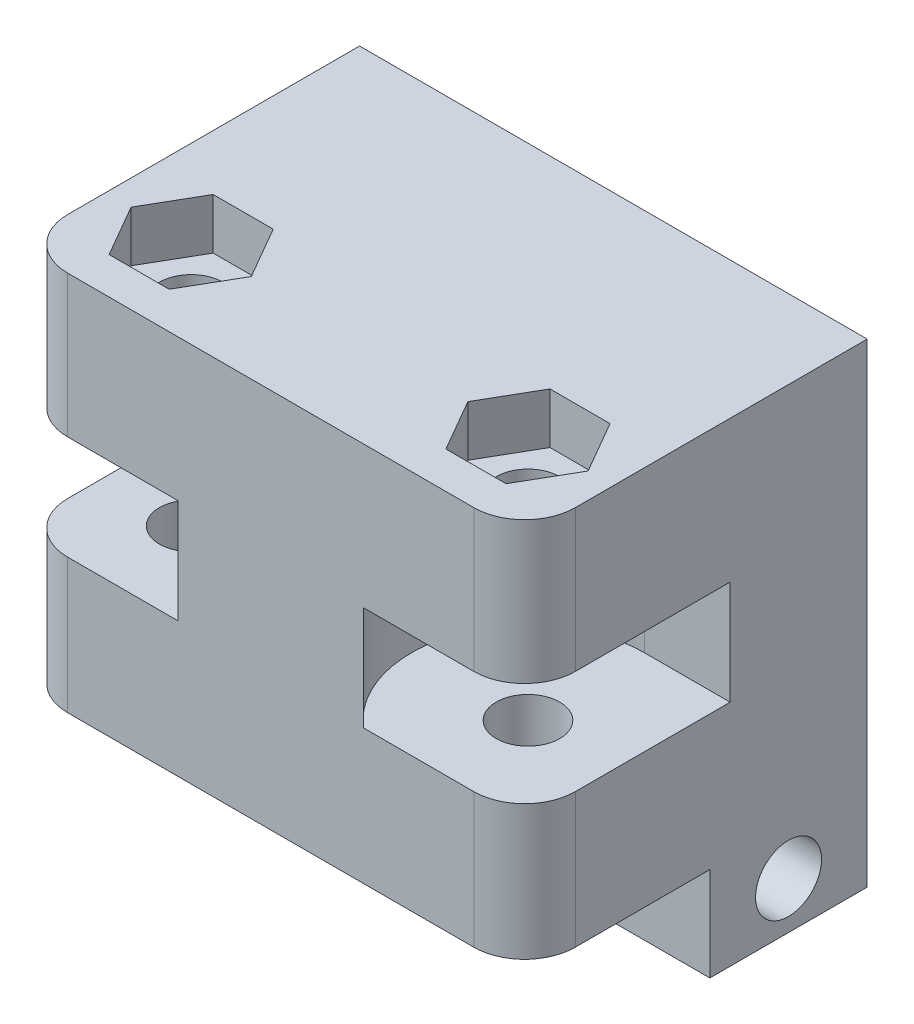
SolidWorks part; units mm, degrees
ref_plane "Front Plane" through (0, 0, 0) normal (0, 0, 1) x (1, 0, 0)
ref_plane "Top Plane" through (0, 0, 0) normal (0, 1, 0) x (1, 0, 0)
ref_plane "Right Plane" through (0, 0, 0) normal (1, 0, 0) x (0, 0, -1)
sketch "Sketch1" plane through (0, 0, 0) normal (0, 1, 0) x (1, 0, 0)
  line L1 (-22.8462, -9.1868) -> (17.1538, -9.1868)
  line L2 (-22.8462, -9.1868) -> (-22.8462, 17.8132)
  line L3 (-22.8462, 17.8132) -> (17.1538, 17.8132)
  line L4 (17.1538, -9.1868) -> (17.1538, 17.8132)
  dimension "D1" = 27
  dimension "D2" = 40
extrude "Boss-Extrude1" add sketch "Sketch1" along normal blind 30
sketch "Sketch2" plane through (0, 0, -17.8132) normal (0, 0, -1) x (-1, 0, 0)
  line L0 (2.8462, 30) -> (2.8462, 0) construction
  line L1 (-8.0864, 4) -> (-0.2064, 4)
  line L2 (-0.2064, 4) -> (-0.2064, 7)
  line L3 (-0.2064, 7) -> (-2.8664, 7)
  line L4 (-2.8664, 7) -> (-2.8664, 8.0087)
  line L5 (-2.8664, 8.0087) -> (-0.2538, 10.6287)
  line L6 (-0.2538, 10.6287) -> (5.9462, 10.6287)
  line L7 (-17.1538, 30) -> (22.8462, 30) construction
  line L8 (-17.1538, 0) -> (22.8462, 0) construction
  line L9 (-8.0864, 4) -> (-8.0864, 26)
  line L10 (-8.0864, 26) -> (-0.2064, 26)
  line L11 (-0.2064, 26) -> (-0.2064, 23)
  line L12 (-0.2064, 23) -> (-2.8664, 23)
  line L13 (-2.8664, 23) -> (-2.8664, 21.9913)
  line L14 (-2.8664, 21.9913) -> (-0.2464, 19.3787)
  line L15 (-0.2464, 19.3787) -> (5.9536, 19.3787)
  line L16 (-17.1538, 15) -> (22.8462, 15) construction
  line L17 (-17.1538, 30) -> (-17.1538, 0) construction
  line L18 (22.8462, 30) -> (22.8462, 0) construction
  line L19 (5.9387, 19.3787) -> (-0.2613, 19.3787)
  line L20 (8.5587, 21.9913) -> (5.9387, 19.3787)
  line L21 (8.5587, 23) -> (8.5587, 21.9913)
  line L22 (5.8987, 23) -> (8.5587, 23)
  line L23 (5.8987, 26) -> (5.8987, 23)
  line L24 (13.7787, 26) -> (5.8987, 26)
  line L25 (13.7787, 4) -> (13.7787, 26)
  line L26 (8.5587, 8.0087) -> (5.9462, 10.6287)
  line L27 (8.5587, 7) -> (8.5587, 8.0087)
  line L28 (5.8987, 7) -> (8.5587, 7)
  line L29 (5.8987, 4) -> (5.8987, 7)
  line L30 (13.7787, 4) -> (5.8987, 4)
  point P26 (-8.0864, 15)
  point P27 (2.8462, 15)
  point P37 (2.8462, 10.6287)
  dimension "D1" = 6.2
  dimension "D2" = 2.62
  dimension "D3" = 3.7
  dimension "D4" = 8.75
  dimension "D5" = 7.88
  dimension "D6" = 22
  dimension "D7" = 5.22
  dimension "D8" = 3
  dimension "D9" = 90
extrude "Cut-Extrude1" cut sketch "Sketch2" against normal blind 10 contours L30 L25 L24 L23 L22 L21 L20 L15 L14 L13 L12 L11 L10 L9 L1 L2 L3 L4 L5 L6 L26 L27 L28 L29 region at (-2.8462, 15.0011, -17.8132)
sketch "Sketch3" plane through (0, 0, 0) normal (0, -1, 0) x (1, 0, 0)
  line L0 (-22.8462, 9.1868) -> (17.1538, 9.1868) construction
  line L1 (17.1538, 9.1868) -> (17.1538, -17.8132) construction
  line L2 (-2.8462, 9.1868) -> (-2.8462, -17.8132) construction
  line L3 (17.1538, -17.8132) -> (-22.8462, -17.8132) construction
  circle A0 centre (10.4238, 2.1868) radius 2.5
  circle A2 centre (-16.1162, 2.1868) radius 2.5
  dimension "D1" = 5
  dimension "D3" = 7
  dimension "D4" = 6.73
extrude "Cut-Extrude2" cut sketch "Sketch3" against normal blind 30
sketch "Sketch8" plane through (0, 0, 0) normal (0, -1, 0) x (1, 0, 0)
  line L0 (4.4539, 9.1868) -> (17.1538, 9.1868)
  line L1 (-22.8462, 9.1868) -> (17.1538, 9.1868) construction
  line L2 (17.1538, 9.1868) -> (17.1538, -7.0132)
  line L3 (17.1538, 9.1868) -> (17.1538, -17.8132) construction
  line L4 (17.1538, -7.0132) -> (10.4238, -7.0132)
  line L6 (-2.8462, -17.8132) -> (-2.8462, 9.1868) construction
  line L7 (17.1538, -17.8132) -> (-22.8462, -17.8132) construction
  line L8 (-22.8462, -7.0132) -> (-16.1162, -7.0132)
  line L9 (-22.8462, 9.1868) -> (-22.8462, -7.0132)
  line L10 (-10.1462, 9.1868) -> (-22.8462, 9.1868)
  arc A0 (10.4238, -7.0132) -> (4.4539, 9.1868) centre (10.4238, 2.1868) cw
  arc A1 (-16.1162, -7.0132) -> (-10.1462, 9.1868) centre (-16.1162, 2.1868) ccw
  circle M6 centre (10.4238, 2.1868) radius 2.5
  circle M7 centre (-16.1162, 2.1868) radius 2.5
  line M8 (-22.8462, 9.1868) -> (-22.8462, -17.8132)
  line M10 (17.1538, -17.8132) -> (17.1538, 9.1868)
  line M11 (17.1538, 9.1868) -> (-22.8462, 9.1868)
  dimension "D1" = 9.2
  dimension "D2" = 6.73
extrude "Cut-Extrude5" cut sketch "Sketch8" against normal blind 8.2 from offset 10.62 contours A0 L4 M10 M11 M6 | M6 | L8 A1 M11 M8 M7 | M7 region at (10.8039, 0, 8.9596) region at (-7.6968, 0, -0.9158) region at (10.4238, 0, 2.1868) region at (-16.1162, 0, 2.1868) offset against normal yes
sketch "Sketch10" plane through (8.0864, 0, 0) normal (-1, 0, 0) x (0, 0, 1)
  line L0 (-17.8132, 30) -> (-17.8132, 0) construction
  line L1 (-17.8132, 18.82) -> (2.1868, 18.82)
  line L2 (-17.8132, 18.82) -> (-17.8132, 10.62)
  line L3 (-17.8132, 10.62) -> (2.1868, 10.62)
  line L4 (2.1868, 18.82) -> (2.1868, 10.62)
  line L5 (-17.8132, 30) -> (9.1868, 30) construction
  dimension "D1" = 20
  dimension "D2" = 11.18
  dimension "D3" = 8.2
extrude "Cut-Extrude7" cut sketch "Sketch10" along normal blind 6.8
sketch "Sketch12" plane through (-13.7787, 0, 0) normal (1, 0, 0) x (0, 0, -1)
  line L1 (17.8132, 18.82) -> (-2.1868, 18.82)
  line L2 (17.8132, 18.82) -> (17.8132, 10.62)
  line L3 (17.8132, 10.62) -> (-2.1868, 10.62)
  line L4 (-2.1868, 18.82) -> (-2.1868, 10.62)
  line L5 (-9.1868, 30) -> (17.8132, 30) construction
  dimension "D1" = 20
  dimension "D2" = 8.2
  dimension "D3" = 11.18
extrude "Cut-Extrude10" cut sketch "Sketch12" along normal blind 6.8
fillet "Fillet1" radius 4 4 edges at (17.1538, 5.31, 9.1868) (17.1538, 24.41, 9.1868) (-22.8462, 5.31, 9.1868) (-22.8462, 24.41, 9.1868)
sketch "Sketch13" plane through (17.1538, 0, 0) normal (1, 0, 0) x (0, 0, -1)
  line L0 (-5.1868, 0) -> (17.8132, 0) construction
  line L1 (17.8132, 30) -> (17.8132, 0) construction
  line L3 (17.8132, 0) -> (5.4132, 0)
  line L4 (17.8132, 0) -> (17.8132, -7.4)
  line L5 (17.8132, -7.4) -> (5.4132, -7.4)
  line L6 (5.4132, 0) -> (5.4132, -7.4)
  circle A0 centre (11.6132, -3.7) radius 2.6
  dimension "D1" = 6.2
  dimension "D2" = 3.7
  dimension "D3" = 5.2
  dimension "D4" = 12.4
  dimension "D5" = 7.4
extrude "Boss-Extrude2" add sketch "Sketch13" against normal up to surface (40 mm away) up to face at (-22.8462, 14.86, -3.6132)
sketch "Sketch14" plane through (0, 0, -5.4132) normal (0, 0, 1) x (1, 0, 0)
  line L0 (-22.8462, -7.4) -> (17.1538, -7.4) construction
  line L1 (-12.8462, -7.4) -> (7.1538, -7.4)
  line L2 (-12.8462, -7.4) -> (-12.8462, 0)
  line L3 (-12.8462, 0) -> (7.1538, 0)
  line L4 (7.1538, -7.4) -> (7.1538, 0)
  line L5 (-18.8462, 0) -> (13.1538, 0) construction
  line L7 (17.1538, 0) -> (17.1538, -7.4) construction
  dimension "D1" = 20
  dimension "D2" = 10
extrude "Cut-Extrude11" cut sketch "Sketch14" against normal up to next
sketch "Sketch15" plane through (0, 30, 0) normal (0, 1, 0) x (1, 0, 0)
  line L1 (12.791, -6.2868) -> (15.1581, -2.1868)
  line L2 (15.1581, -2.1868) -> (12.791, 1.9132)
  line L3 (12.791, 1.9132) -> (8.0567, 1.9132)
  line L4 (8.0567, 1.9132) -> (5.6896, -2.1868)
  line L5 (5.6896, -2.1868) -> (8.0567, -6.2868)
  line L6 (8.0567, -6.2868) -> (12.791, -6.2868)
  line L7 (-13.749, -6.2868) -> (-11.3819, -2.1868)
  line L8 (-11.3819, -2.1868) -> (-13.749, 1.9132)
  line L9 (-13.749, 1.9132) -> (-18.4833, 1.9132)
  line L10 (-18.4833, 1.9132) -> (-20.8504, -2.1868)
  line L11 (-20.8504, -2.1868) -> (-18.4833, -6.2868)
  line L12 (-18.4833, -6.2868) -> (-13.749, -6.2868)
  circle A0 centre (-16.1162, -2.1868) radius 2.5 construction
  circle A1 centre (10.4238, -2.1868) radius 2.5 construction
  circle A2 centre (-16.1162, -2.1868) radius 2.5
  circle A3 centre (10.4238, -2.1868) radius 2.5
  circle A4 centre (10.4238, -2.1868) radius 4.1 construction
  circle A5 centre (-16.1162, -2.1868) radius 4.1 construction
  dimension "D2" = 8.2
  dimension "D1" = 8.2
extrude "Cut-Extrude12" cut sketch "Sketch15" against normal blind 4
sketch "Sketch16" plane through (0, 0, 0) normal (0, -1, 0) x (1, 0, 0)
  line L1 (-13.749, -1.9132) -> (-11.3819, 2.1868)
  line L2 (-11.3819, 2.1868) -> (-13.749, 6.2868)
  line L3 (-13.749, 6.2868) -> (-18.4833, 6.2868)
  line L4 (-18.4833, 6.2868) -> (-20.8504, 2.1868)
  line L5 (-20.8504, 2.1868) -> (-18.4833, -1.9132)
  line L6 (-18.4833, -1.9132) -> (-13.749, -1.9132)
  line L7 (12.791, -1.9132) -> (15.1581, 2.1868)
  line L8 (15.1581, 2.1868) -> (12.791, 6.2868)
  line L9 (12.791, 6.2868) -> (8.0567, 6.2868)
  line L10 (8.0567, 6.2868) -> (5.6896, 2.1868)
  line L11 (5.6896, 2.1868) -> (8.0567, -1.9132)
  line L12 (8.0567, -1.9132) -> (12.791, -1.9132)
  circle A0 centre (10.4238, 2.1868) radius 2.5 construction
  circle A1 centre (-16.1162, 2.1868) radius 2.5 construction
  circle A2 centre (10.4238, 2.1868) radius 2.5
  circle A3 centre (-16.1162, 2.1868) radius 2.5
  circle A4 centre (-16.1162, 2.1868) radius 4.1 construction
  circle A5 centre (10.4238, 2.1868) radius 4.1 construction
  dimension "D1" = 8.2
  dimension "D2" = 8.2
extrude "Cut-Extrude13" cut sketch "Sketch16" against normal blind 4
